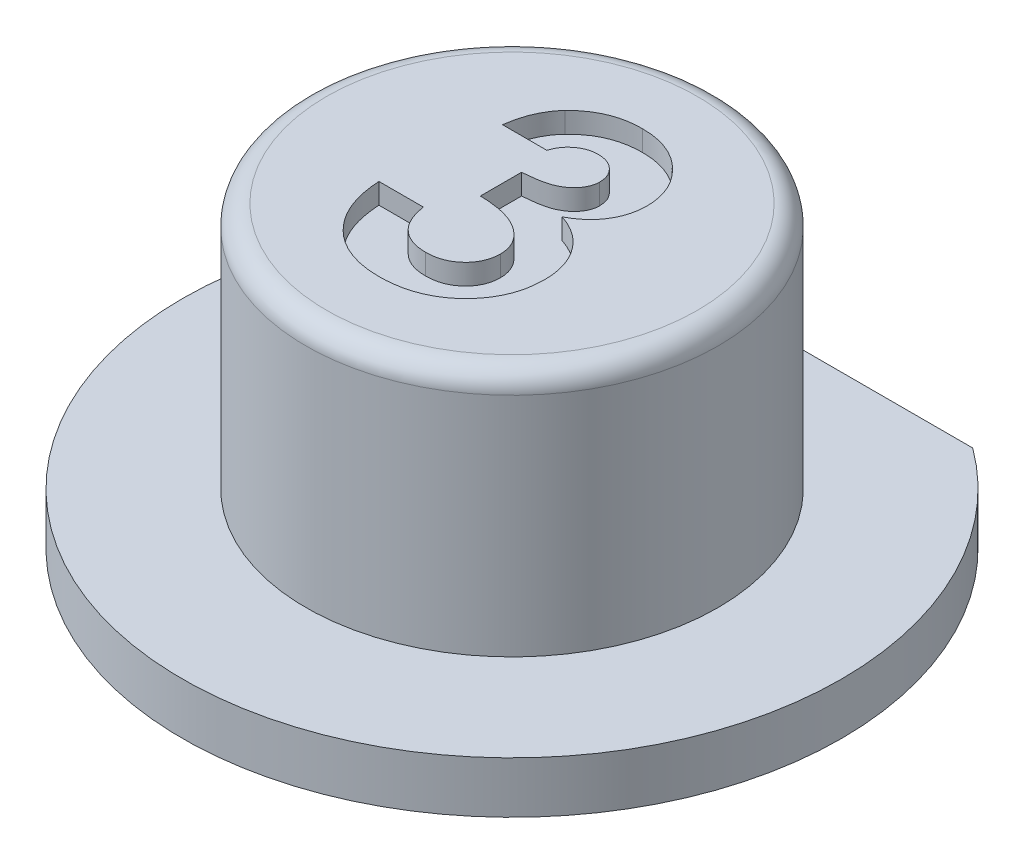
SolidWorks part; units mm, degrees
ref_plane "Front Plane" through (0, 0, 0) normal (0, 0, 1) x (1, 0, 0)
ref_plane "Top Plane" through (0, 0, 0) normal (0, 1, 0) x (1, 0, 0)
ref_plane "Right Plane" through (0, 0, 0) normal (1, 0, 0) x (0, 0, -1)
sketch "Sketch1" plane through (0, 0, 0) normal (0, 0, 1) x (1, 0, 0)
  line L1 (0, 7.25) -> (5, 7.25)
  line L2 (5, 7.25) -> (5, 1.25)
  line L3 (5, 1.25) -> (8, 1.25)
  line L4 (8, 1.25) -> (8, 0)
  line L6 (0, 7.25) -> (0, 6.9292) construction
  line L7 (0, 7.25) -> (0, 0)
  line L10 (0, 0) -> (8, 0)
  dimension "D1" = 5
  dimension "D2" = 3
  dimension "D3" = 6
  dimension "D4" = 1.25
revolve "Revolve1" add sketch "Sketch1" angle 360 about L6
sketch "Sketch2" plane through (0, 0, 0) normal (0, -1, 0) x (1, 0, 0)
  line L1 (-1.25, -1.75) -> (1.25, -1.75)
  line L2 (-1.25, -1.75) -> (-1.25, 1.75)
  line L3 (-1.25, 1.75) -> (1.25, 1.75)
  line L4 (1.25, -1.75) -> (1.25, 1.75)
  line L5 (-1.25, -1.75) -> (1.25, 1.75) construction
  line L6 (-1.25, 1.75) -> (1.25, -1.75) construction
  point P0 (0, 0)
  dimension "D1" = 2.5
  dimension "D2" = 3.5
extrude "Cut-Extrude1" cut sketch "Sketch2" against normal blind 3.5 contours L3 L4 L1 L2
fillet "Fillet1" radius 0.5 1 edges at (-5, 7.25, 0)
sketch "Sketch3" plane through (0, 7.25, 0) normal (0, 1, 0) x (1, 0, 0)
  line L0 (-3.3541, -3) -> (3.3541, -3) construction
  line L1 (0, 0) -> (0, -3) construction
  circle A0 centre (0, 0) radius 4.5 construction
  text T0 "3" font "Century Gothic" height 6
  dimension "D1" = 3
extrude "Cut-Extrude2" cut sketch "Sketch3" against normal blind 0.5
sketch "Sketch4" plane through (0, 0, 0) normal (0, -1, 0) x (-1, 0, 0)
  line L0 (5, 6.4497) -> (-5, 6.4497)
  line L1 (-5, 6.4497) -> (-5, 9.4497)
  line L2 (-5, 9.4497) -> (5, 9.4497)
  line L3 (5, 9.4497) -> (5, 6.4497)
  line L4 (0, 0) -> (0, 6.4497) construction
  dimension "D1" = 0.5
  dimension "D2" = 10
  dimension "D3" = 3
extrude "Cut-Extrude3" cut sketch "Sketch4" against normal through all
